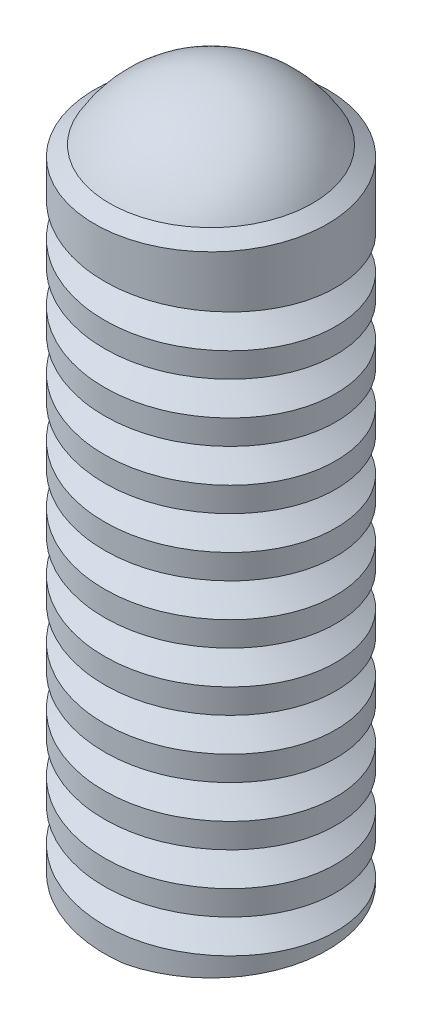
SolidWorks part; units mm, degrees
ref_plane "Front Plane" through (0, 0, 0) normal (0, 0, 1) x (1, 0, 0)
ref_plane "Top Plane" through (0, 0, 0) normal (0, 1, 0) x (1, 0, 0)
ref_plane "Right Plane" through (0, 0, 0) normal (1, 0, 0) x (0, 0, -1)
sketch "Sketch1" plane through (0, 0, 0) normal (0, 1, 0) x (1, 0, 0)
  circle A0 centre (0, 0) radius 1
  dimension "D1" = 2
extrude "Body" add sketch "Sketch1" along normal blind 5.75
ref_plane "Ball Depth" through (0, 5, 0) normal (0, 1, 0) x (1, 0, 0)
sketch "Sketch2" plane through (0, 5, 0) normal (0, 1, 0) x (1, 0, 0)
  line L0 (-0.9992, -0.0403) -> (0.9992, 0.0403) construction
  line L1 (0.9992, 0.0403) -> (-0.9992, -0.0403)
  arc A0 (-0.9992, -0.0403) -> (0.9992, 0.0403) centre (0, 0) ccw
  point P0 (0, 0)
revolve "Ball Point" add sketch "Sketch2" angle 360 about L0
chamfer "Head Chamfer" distance 0.35 distance2 0.5 1 edges at (0, 5.75, 1) first distance on face at (0, 5.75, 1)
sketch "Sketch4" plane through (0, 0, 0) normal (0, -1, 0) x (1, 0, 0)
  circle A0 centre (0, 0) radius 1
curve "Thread Helix" pitch 0.5 height 5 radius 1 left hand yes centre (0, 0, 0) axis (0, 1, 0) start towards (0, 0, -1)
sketch "Sketch5" plane through (0, 0, 0) normal (0, 0, 1) x (1, 0, 0)
  line L0 (0, 0) -> (-1, 0) construction
  line L5 (-1.125, 0.2165) -> (-1.125, -0.2165)
  line L6 (-1.125, -0.2165) -> (-0.75, 0)
  line L7 (-0.75, 0) -> (-1.125, 0.2165)
  circle A0 centre (-1, 0) radius 0.125 construction
  point P0 (-1, 0)
  point P1 (0, 0)
  dimension "D1" = 0.25
sweep "Screw Thread" cut profiles "Sketch5" path "Thread Helix" align with end faces yes
